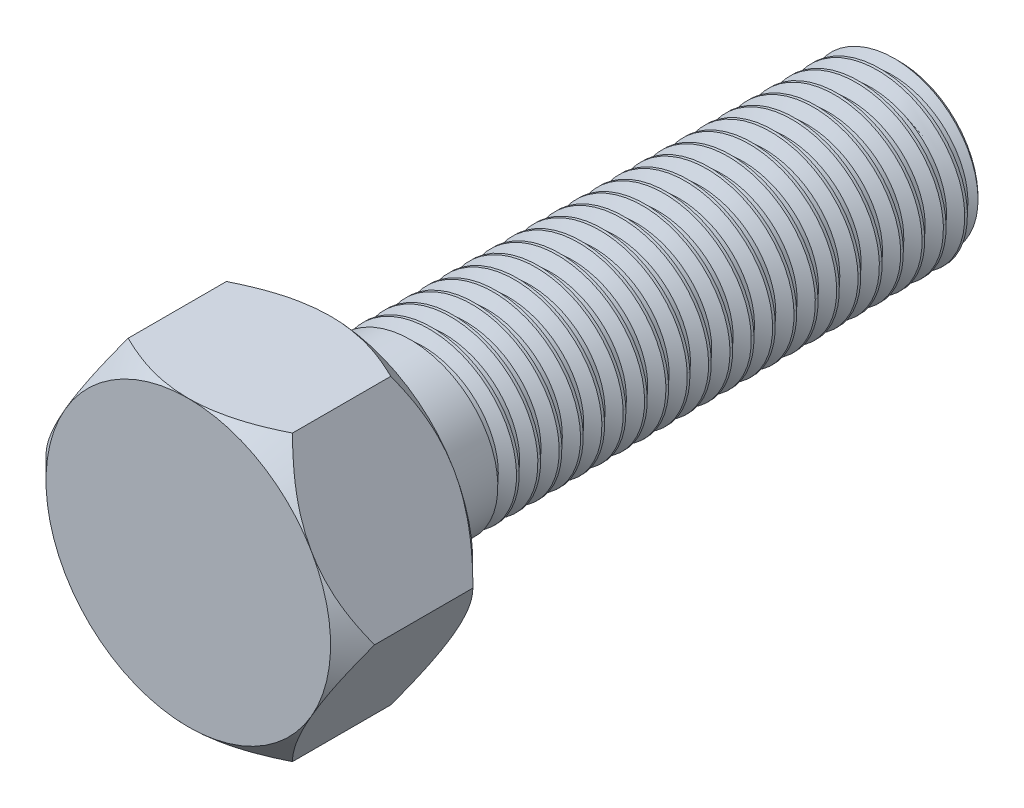
SolidWorks part; units mm, degrees
ref_plane "Front Plane" through (0, 0, 0) normal (0, 0, 1) x (1, 0, 0)
ref_plane "Top Plane" through (0, 0, 0) normal (0, 1, 0) x (1, 0, 0)
ref_plane "Right Plane" through (0, 0, 0) normal (1, 0, 0) x (0, 0, -1)
sketch "Sketch1" plane through (0, 0, 0) normal (0, 0, 1) x (1, 0, 0)
  line L7 (5.7735, -10) -> (11.547, 0)
  line L8 (11.547, 0) -> (5.7735, 10)
  line L9 (5.7735, 10) -> (-5.7735, 10)
  line L10 (-5.7735, 10) -> (-11.547, 0)
  line L11 (-11.547, 0) -> (-5.7735, -10)
  line L12 (-5.7735, -10) -> (5.7735, -10)
  circle A0 centre (0, 0) radius 10 construction
  dimension "D1" = 20
extrude "Boss-Extrude1" add sketch "Sketch1" along normal mid plane 10
sketch "Sketch2" plane through (0, 0, 5) normal (0, 0, 1) x (1, 0, 0)
  line L0 (-5.7735, 10) -> (-11.547, 0) construction
  circle A0 centre (0, 0) radius 10
extrude "Cut-Extrude1" cut sketch "Sketch2" against normal blind 9 draft 45 flip side to cut
mirror "Mirror1" about plane through (0, 0, 0) normal (0, 0, 1) of "Cut-Extrude1"
sketch "Sketch3" plane through (0, 0, -5) normal (0, 0, -1) x (-1, 0, 0)
  circle A0 centre (0, 0) radius 6
  dimension "D1" = 12
extrude "Boss-Extrude2" add sketch "Sketch3" along normal blind 40
chamfer "Chamfer1" distance 0.5 angle 45 1 edges at (-6, 0, -45)
thread "Thread1" pitch 1.5 start angle 0, offset 5, length 0, pitch 1.5, diameter 12
ref_plane "Plane2" through (-6, 0, -10) normal (0, -1, 0) x (-1, 0, 0)
sketch "Thread Profile2" plane through (-6, 0, -10) normal (0, -1, 0) x (-1, 0, 0)
  line L0 (0, 0) -> (0, 1.5) construction
  line L11 (0, 0) -> (0, 1.3125)
  line L12 (0, 1.3125) -> (-0.8119, 0.8437)
  line L13 (-0.8119, 0.8437) -> (-0.8119, 0.4687)
  line L15 (-0.8119, 0.4687) -> (0, 0)
  line L17 (-0.8119, 0.6562) -> (0, 0.6562) construction
  point P2 (0, 0)
  dimension "Pitch" = 1.5
  dimension "Profile_Angle" = 60
  dimension "Profile_Land" = 0.375
  dimension "Profile_Height" = 0.8119
sketch "Sketch12" plane through (0, 0, 0) normal (0, 1, 0) x (1, 0, 0)
  line L4 (-6, 10) -> (-5.1881, 10.4687)
  line L5 (-5.1881, 10.4687) -> (-5.1881, 10.8437)
  line L6 (-5.1881, 10.8437) -> (-6, 11.3125)
  line L7 (-6, 11.3125) -> (-6, 10)
  line L8 (-6, 10) -> (-5.1881, 10.4687)
  line L9 (-5.1881, 10.4687) -> (-5.1881, 10.8437)
  line L10 (-5.1881, 10.8437) -> (-6, 11.3125)
  line L11 (-6, 11.3125) -> (-6, 10)
  dimension "D1" = 0
extrude "Cut-Extrude2" cut sketch "Sketch12" against normal through all
